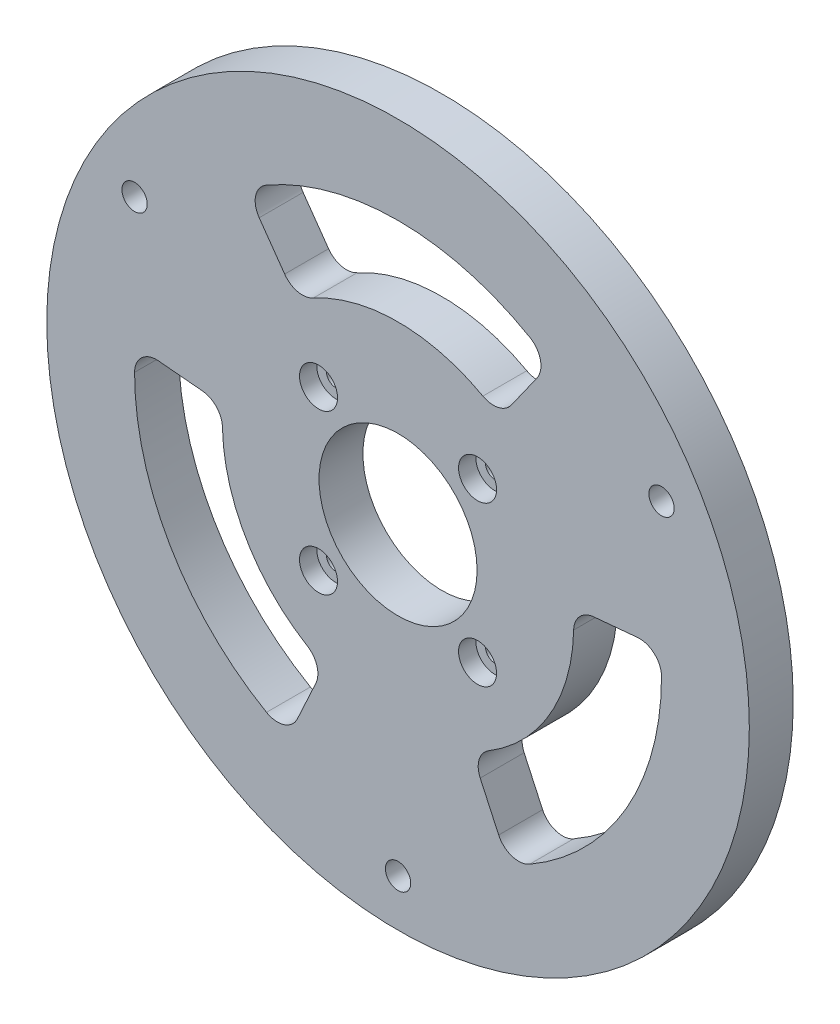
SolidWorks part; units mm, degrees
material "Acrylic (Medium-high impact)"
ref_plane "Front Plane" through (0, 0, 0) normal (0, 0, 1) x (1, 0, 0)
ref_plane "Top Plane" through (0, 0, 0) normal (0, 1, 0) x (1, 0, 0)
ref_plane "Right Plane" through (0, 0, 0) normal (1, 0, 0) x (0, 0, -1)
sketch "Sketch1" plane through (0, 0, 0) normal (0, 0, 1) x (1, 0, 0)
  circle A0 centre (0, 0) radius 50.8
  dimension "D1" = 101.6
extrude "Boss-Extrude1" add sketch "Sketch1" along normal blind 6.35
sketch "Sketch2" plane through (0, 0, 6.35) normal (0, 0, 1) x (1, 0, 0)
  circle A0 centre (0, 0) radius 11.43
  dimension "D1" = 22.86
extrude "Cut-Extrude1" cut sketch "Sketch2" against normal through all
hole_wizard "CBORE for M2.5 SHCS1" positions "Sketch3" profile "Sketch5" counterbore size "M2.5" standard "ANSI Metric"
sketch "Sketch3" plane through (0, 0, 6.35) normal (0, 0, 1) x (1, 0, 0)
  line L1 (-11.5, -11.5) -> (11.5, -11.5)
  line L2 (-11.5, -11.5) -> (-11.5, 11.5)
  line L3 (-11.5, 11.5) -> (11.5, 11.5)
  line L4 (11.5, -11.5) -> (11.5, 11.5)
  line L5 (-11.5, -11.5) -> (11.5, 11.5) construction
  line L6 (-11.5, 11.5) -> (11.5, -11.5) construction
  point P1 (0, 0)
  point P2 (11.5, 11.5)
  point P59 (-11.5, -11.5)
  point P60 (-11.5, 11.5)
  point P61 (11.5, -11.5)
  dimension "D1" = 23
sketch "Sketch5" plane through (0, 0, 6.35) normal (1, 0, 0) x (0, -1, 0)
  line L0 (0, 0) -> (0, 10.9712)
  line L1 (0, 10.9712) -> (1.35, 10.16)
  line L2 (1.35, 10.16) -> (1.35, 2.5)
  line L3 (1.35, 2.5) -> (2.75, 2.5)
  line L4 (2.75, 2.5) -> (2.75, 0)
  line L5 (2.75, 0) -> (0, 0)
  line L10 (0, 10.9712) -> (-1.35, 10.16) construction
  line L11 (0, -6.35) -> (0, 107.95) construction
  dimension "Hole Dia." = 2.7
  dimension "Hole Depth" = 10.16
  dimension "C'Bore Dia." = 5.5
  dimension "C'Bore Depth" = 2.5
  dimension "Drill Angle" = 118
hole_wizard "#6 Clearance Hole1" positions "Sketch7" profile "Sketch9" hole size "#6" standard "ANSI Inch"
sketch "Sketch7" plane through (0, 0, 6.35) normal (0, 0, 1) x (1, 0, 0)
  line L1 (0, -43.9941) -> (38.1, 21.997)
  line L2 (38.1, 21.997) -> (-38.1, 21.997)
  line L3 (-38.1, 21.997) -> (0, -43.9941)
  line L8 (-11.5, 11.5) -> (11.5, 11.5) construction
  circle A0 centre (0, 0) radius 21.997 construction
  point P3 (0, -43.9941)
  point P4 (38.1, 21.997)
  point P5 (-38.1, 21.997)
  dimension "D1" = 76.2
sketch "Sketch9" plane through (-38.1, 21.997, 6.35) normal (1, 0, 0) x (0, -1, 0)
  line L0 (0, 0) -> (0, 11.2589)
  line L1 (0, 11.2589) -> (1.8288, 10.16)
  line L2 (1.8288, 10.16) -> (1.8288, 0)
  line L5 (1.8288, 0) -> (0, 0)
  line L10 (0, 11.2589) -> (-1.8288, 10.16) construction
  line L11 (0, -6.35) -> (0, 107.95) construction
  dimension "Hole Dia." = 3.6576
  dimension "Hole Depth" = 10.16
  dimension "Drill Angle" = 118
fillet "Fillet1" [suppressed] radius 0.508
sketch "Sketch10" plane through (0, 0, 6.35) normal (0, 0, 1) x (1, 0, 0)
  line L0 (0, 0) -> (-21.9974, 31.1083) construction
  line L1 (0, 0) -> (21.9974, 31.1083) construction
  line L2 (14.6649, 20.7388) -> (21.9974, 31.1083)
  line L3 (-14.6649, 20.7388) -> (-21.9974, 31.1083)
  circle A0 centre (0, 0) radius 25.4 construction
  circle A1 centre (0, 0) radius 38.1 construction
  arc A4 (-21.9974, 31.1083) -> (21.9974, 31.1083) centre (0, 0) cw
  arc A5 (-14.6649, 20.7388) -> (14.6649, 20.7388) centre (0, 0) cw
  circle A6 centre (11.5, 11.5) radius 2.75 construction
  circle A7 centre (-11.5, 11.5) radius 2.75 construction
  dimension "D1" = 50.8
  dimension "D2" = 12.7
extrude "Cut-Extrude2" cut sketch "Sketch10" against normal through all
fillet "Fillet2" radius 3.175 4 edges at (-14.6649, 20.7388, 3.175) (14.6649, 20.7388, 3.175) (21.9974, 31.1083, 3.175) (-21.9974, 31.1083, 3.175)
pattern_circular "CirPattern1" count 3 over 360 about axis through (0, 0, 6.35) along (0, 0, 1) of "Cut-Extrude2", "Fillet2"
